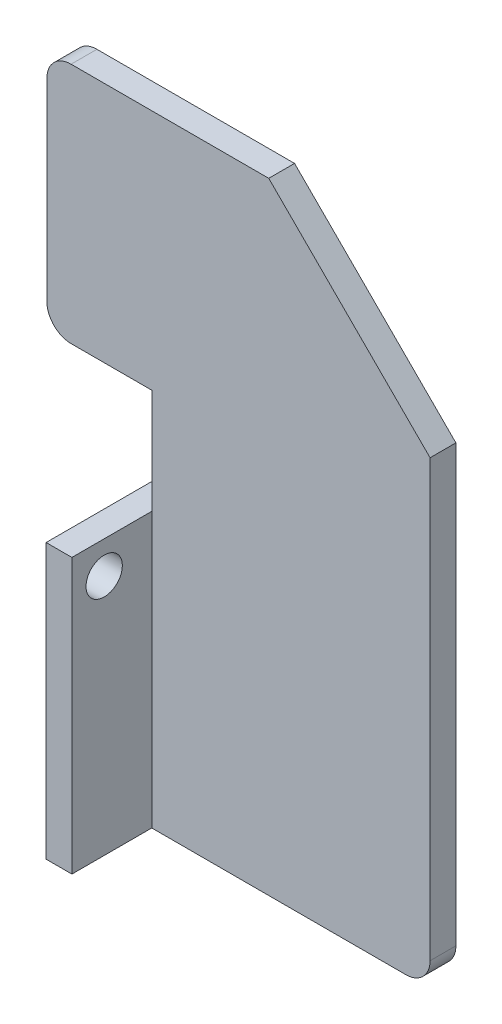
SolidWorks part; units mm, degrees
ref_plane "正面" through (0, 0, 0) normal (0, 0, 1) x (1, 0, 0)
ref_plane "平面" through (0, 0, 0) normal (0, 1, 0) x (1, 0, 0)
ref_plane "右側面" through (0, 0, 0) normal (1, 0, 0) x (0, 0, -1)
sketch "ｽｹｯﾁ1" plane through (0, 0, 0) normal (0, 0, 1) x (1, 0, 0)
  line L0 (3.2, 0) -> (34.7, 0)
  line L1 (37.7, 3) -> (37.7, 57)
  line L2 (37.7, 57) -> (17.7, 77)
  line L3 (17.7, 77) -> (-6.8, 77)
  line L4 (-9.8, 74) -> (-9.8, 50)
  line L5 (-6.8, 47) -> (3.2, 47)
  line L6 (3.2, 47) -> (3.2, 0)
  arc A0 (34.7, 0) -> (37.7, 3) centre (34.7, 3) ccw
  arc A1 (-6.8, 77) -> (-9.8, 74) centre (-6.8, 74) ccw
  arc A2 (-9.8, 50) -> (-6.8, 47) centre (-6.8, 50) ccw
extrude "ﾎﾞｽ - 押し出し1" add sketch "ｽｹｯﾁ1" against normal blind 1.6 and the other way blind 1.6
sketch "ｽｹｯﾁ2" plane through (0, 0, 0) normal (0, 0, 1) x (1, 0, 0)
  line L0 (3.2, 47) -> (3.2, 0) construction
  line L1 (0, 0) -> (3.2, 0)
  line L2 (0, 0) -> (0, 34)
  line L3 (0, 34) -> (3.2, 34)
  line L4 (3.2, 0) -> (3.2, 34)
extrude "ﾎﾞｽ - 押し出し2" add sketch "ｽｹｯﾁ2" against normal blind 11.5 and the other way blind 11.5
sketch "ｽｹｯﾁ3" plane through (0, 0, 0) normal (1, 0, 0) x (0, 0, -1)
  circle A0 centre (-7.5, 30) radius 2.25
  circle A1 centre (7.5, 4) radius 2.25
extrude "ｶｯﾄ - 押し出し1" cut sketch "ｽｹｯﾁ3" against normal through all and the other way through all
